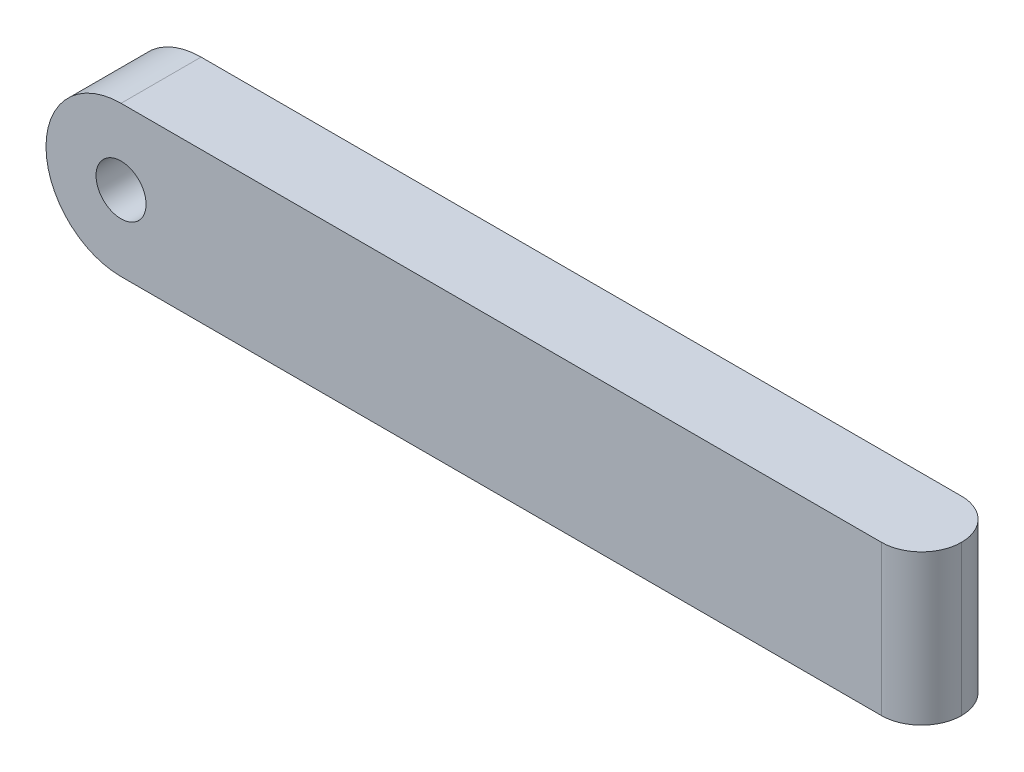
SolidWorks part; units mm, degrees
ref_plane "Plan de face" through (0, 0, 0) normal (0, 0, 1) x (1, 0, 0)
ref_plane "Plan de dessus" through (0, 0, 0) normal (0, 1, 0) x (1, 0, 0)
ref_plane "Plan de droite" through (0, 0, 0) normal (1, 0, 0) x (0, 0, -1)
sketch "Esquisse1" plane through (0, 0, 0) normal (0, 0, 1) x (1, 0, 0)
  line L1 (0, 7.5) -> (80, 7.5)
  line L2 (0, 7.5) -> (0, -7.5) construction
  line L3 (0, -7.5) -> (80, -7.5)
  line L4 (80, 7.5) -> (80, -7.5)
  arc A0 (0, 7.5) -> (0, -7.5) centre (0, 0) ccw
  circle A1 centre (0, 0) radius 2.5
  dimension "D2" = 5
  dimension "D3" = 80
  dimension "D4" = 15
extrude "Boss.-Extru.1" add sketch "Esquisse1" along normal blind 8
fillet "Congé1" radius 4 2 edges at (80, 0, 0) (80, 0, 8)
